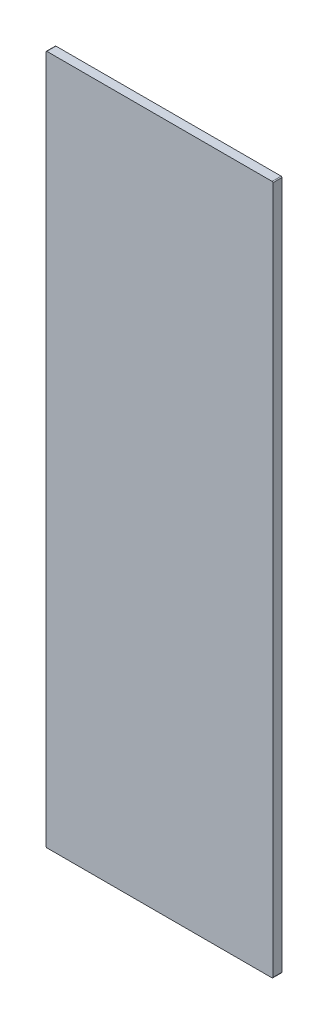
SolidWorks part; units mm, degrees
ref_plane "Front Plane" through (0, 0, 0) normal (0, 0, 1) x (1, 0, 0)
ref_plane "Top Plane" through (0, 0, 0) normal (0, 1, 0) x (1, 0, 0)
ref_plane "Right Plane" through (0, 0, 0) normal (1, 0, 0) x (0, 0, -1)
sketch "Sketch1" plane through (0, 0, 0) normal (0, 0, 1) x (1, 0, 0)
  line L0 (45, -760) -> (-45, -760) construction
  line L1 (204, 0) -> (-44, 0)
  line L2 (205, -1) -> (205, -759)
  line L3 (204, -760) -> (-44, -760)
  line L4 (-45, -1) -> (-45, -759)
  line L5 (-45, -760) -> (-45, 0) construction
  arc A0 (-44, 0) -> (-45, -1) centre (-44, -1) ccw
  arc A1 (204, 0) -> (205, -1) centre (204, -1) cw
  arc A2 (205, -759) -> (204, -760) centre (204, -759) cw
  arc A3 (-44, -760) -> (-45, -759) centre (-44, -759) cw
  point P13 (205, 0)
  point P18 (-45, -760)
  dimension "D1" = 1
extrude "Boss-Extrude1" add sketch "Sketch1" along normal blind 10
